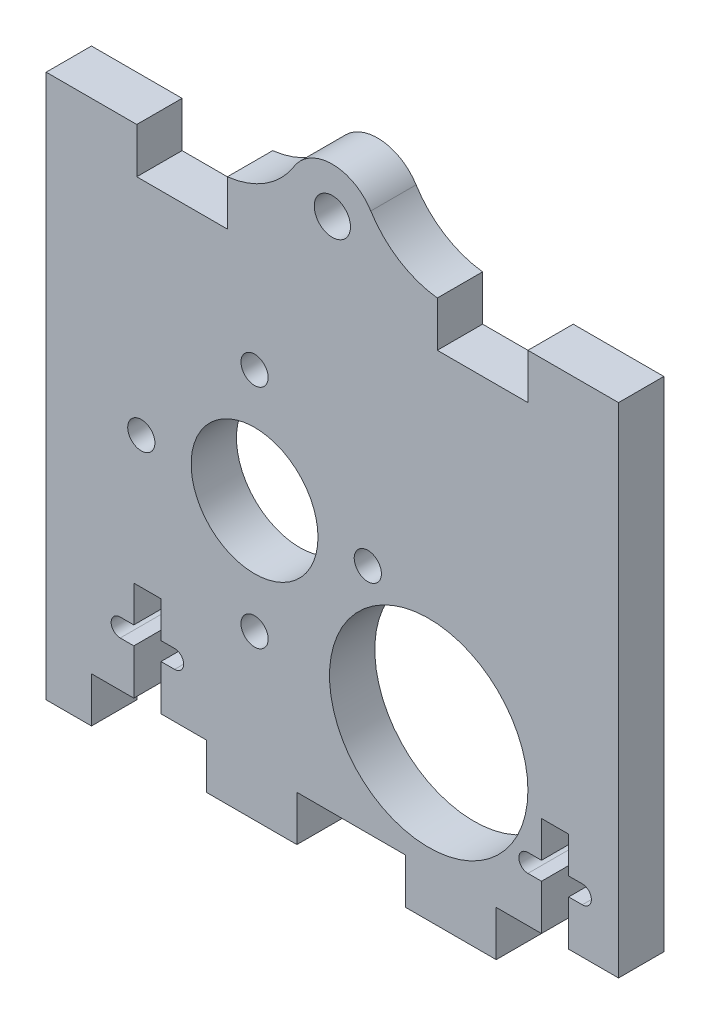
SolidWorks part; units mm, degrees
ref_plane "Front Plane" through (0, 0, 0) normal (0, 0, 1) x (1, 0, 0)
ref_plane "Top Plane" through (0, 0, 0) normal (0, 1, 0) x (1, 0, 0)
ref_plane "Right Plane" through (0, 0, 0) normal (1, 0, 0) x (0, 0, -1)
sketch "Sketch8" plane through (0, 0, 0) normal (0, 0, 1) x (1, 0, 0)
  line L0 (-31.586, -24.275) -> (31.586, -24.275)
  line L1 (-31.586, -24.275) -> (-31.586, 30.725)
  line L2 (-31.586, 30.725) -> (-8.414, 30.725)
  line L3 (31.586, -24.275) -> (31.586, -9.275)
  line L4 (27.586, -18.275) -> (21.586, -18.275) construction
  line L5 (31.586, -24.275) -> (21.586, -24.275)
  line L6 (26.086, -24.275) -> (23.086, -24.275)
  line L7 (26.086, -24.275) -> (26.086, -13.275)
  line L8 (26.086, -13.275) -> (23.086, -13.275)
  line L9 (23.086, -24.275) -> (23.086, -13.275)
  line L10 (27.586, -19.275) -> (21.586, -19.275)
  line L11 (27.586, -17.275) -> (21.586, -17.275)
  line L12 (24.586, -13.275) -> (24.586, -18.275) construction
  line L13 (24.586, -18.275) -> (24.586, -24.275) construction
  line L14 (-18.914, -24.275) -> (-21.914, -24.275)
  line L15 (-18.914, -24.275) -> (-18.914, -13.275)
  line L16 (-18.914, -13.275) -> (-21.914, -13.275)
  line L17 (-21.914, -24.275) -> (-21.914, -13.275)
  line L18 (-20.414, -13.275) -> (-20.414, -18.275) construction
  line L19 (-20.414, -18.275) -> (-20.414, -24.275) construction
  line L20 (-17.414, -18.275) -> (-23.414, -18.275) construction
  line L21 (-17.414, -19.275) -> (-23.414, -19.275)
  line L22 (-17.414, -17.275) -> (-23.414, -17.275)
  line L23 (-17.414, 24.725) -> (-23.414, 24.725) construction
  line L24 (-17.414, 25.725) -> (-23.414, 25.725)
  line L25 (-17.414, 23.725) -> (-23.414, 23.725)
  line L26 (-20.414, 24.725) -> (-20.414, 30.725) construction
  line L27 (-20.414, 19.725) -> (-20.414, 24.725) construction
  line L28 (-21.914, 30.725) -> (-21.914, 19.725)
  line L29 (-18.914, 19.725) -> (-21.914, 19.725)
  line L30 (-18.914, 30.725) -> (-18.914, 19.725)
  line L31 (-18.914, 30.725) -> (-21.914, 30.725)
  circle A0 centre (-8.586, 1.275) radius 7
  circle A1 centre (10.636, -11.325) radius 10.95
  circle A2 centre (-8.586, 13.775) radius 1.5
  circle A3 centre (3.914, 1.275) radius 1.5
  circle A4 centre (-8.586, -11.225) radius 1.5
  circle A5 centre (-21.086, 1.275) radius 1.5
  arc A6 (-8.414, 30.725) -> (31.586, -9.275) centre (-8.414, -9.275) cw
  arc A7 (27.586, -19.275) -> (27.586, -17.275) centre (27.586, -18.275) ccw
  arc A8 (21.586, -17.275) -> (21.586, -19.275) centre (21.586, -18.275) ccw
  arc A9 (-17.414, -19.275) -> (-17.414, -17.275) centre (-17.414, -18.275) ccw
  arc A10 (-23.414, -17.275) -> (-23.414, -19.275) centre (-23.414, -18.275) ccw
  arc A11 (-17.414, 25.725) -> (-17.414, 23.725) centre (-17.414, 24.725) cw
  arc A12 (-23.414, 23.725) -> (-23.414, 25.725) centre (-23.414, 24.725) cw
  point P25 (24.586, -18.275)
  point P41 (-20.414, -18.275)
  point P51 (-20.414, 24.725)
  dimension "D1" = 14
  dimension "D2" = 40
  dimension "D3" = 3
  dimension "D4" = 11
  dimension "D5" = 2
  dimension "D6" = 8
  dimension "D7" = 5
  dimension "D8" = 55
extrude "Boss-Extrude1" add sketch "Sketch8" along normal blind 5 contours L25 A12 L24 L28 L2 L1 L0 L17 L21 A10 L22 L16 L15 A9 L9 L10 A8 L11 L8 L7 A7 L3 A6 L30 A11 L29 A5 A4 A3 A2 region at (-30.7484, 3.225, 0)
sketch "Sketch9" plane through (0, 0, 0) normal (0, 0, -1) x (-1, 0, 0)
  line L0 (18.914, -24.275) -> (-23.086, -24.275) construction
  line L1 (-18.086, -24.275) -> (-8.086, -24.275)
  line L2 (-18.086, -24.275) -> (-18.086, -29.275)
  line L3 (-18.086, -29.275) -> (-8.086, -29.275)
  line L4 (-8.086, -24.275) -> (-8.086, -29.275)
  line L5 (-23.086, -24.275) -> (-23.086, -19.275) construction
  line L6 (3.914, -24.275) -> (3.914, -29.275)
  line L7 (3.914, -24.275) -> (13.914, -24.275)
  line L8 (13.914, -24.275) -> (13.914, -29.275)
  line L9 (3.914, -29.275) -> (13.914, -29.275)
  line L10 (18.914, -24.275) -> (18.914, -19.275) construction
  line L11 (-31.586, -24.275) -> (-31.586, -9.275) construction
  line L12 (31.586, 30.725) -> (-31.586, 30.725)
  line L13 (31.586, 30.725) -> (31.586, 11.7466)
  line L14 (31.586, 11.7466) -> (10.7623, 11.7466)
  line L15 (-31.586, 30.725) -> (-31.586, 11.7466)
  line L16 (6.4097, 11.7466) -> (-17.7432, 11.7466)
  line L19 (-31.586, 11.7466) -> (-31.586, -2.995)
  line L20 (31.586, -24.275) -> (26.586, -24.275)
  line L21 (31.586, -24.275) -> (31.586, -29.275)
  line L22 (31.586, -29.275) -> (26.586, -29.275)
  line L23 (26.586, -24.275) -> (26.586, -29.275)
  line L24 (-26.161, -2.995) -> (-17.7432, -2.995)
  line L25 (-17.7432, 11.7466) -> (-17.7432, -2.995)
  line L26 (-31.586, -9.275) -> (-26.161, -9.275)
  line L27 (-31.586, -9.275) -> (-31.586, -2.995)
  line L29 (-26.161, -9.275) -> (-26.161, -2.995)
  arc A0 (10.7623, 11.7466) -> (6.4097, 11.7466) centre (8.586, 13.775) ccw
  circle A1 centre (-10.636, -11.325) radius 10.95 construction
  dimension "D1" = 5
  dimension "D2" = 5
  dimension "D3" = 10
  dimension "D5" = 5
  dimension "D10" = 5
  dimension "D4" = 2
extrude "Boss-Extrude2" add sketch "Sketch9" against normal blind 5
sketch "Sketch10" plane through (0, 0, 0) normal (0, 0, -1) x (-1, 0, 0)
  arc A0 (0.2424, -12.5751) -> (-7.4428, -0.8509) centre (8.586, 1.275) ccw
  arc A1 (0.2424, -12.5751) -> (-7.4428, -0.8509) centre (-10.636, -11.325) ccw
extrude "Boss-Extrude3" [suppressed] add sketch "Sketch10" against normal blind 5
sketch "Sketch11" plane through (0, 0, 5) normal (0, 0, 1) x (1, 0, 0)
  line L0 (-31.586, 30.725) -> (31.586, 30.725) construction
  line L1 (-21.586, 30.725) -> (-11.586, 30.725)
  line L2 (-21.586, 30.725) -> (-21.586, 25.725)
  line L3 (-21.586, 25.725) -> (-11.586, 25.725)
  line L4 (-11.586, 30.725) -> (-11.586, 25.725)
  line L5 (-31.586, -29.275) -> (-31.586, 30.725) construction
  line L6 (21.586, 30.725) -> (11.586, 30.725)
  line L7 (21.586, 30.725) -> (21.586, 25.725)
  line L8 (21.586, 25.725) -> (11.586, 25.725)
  line L9 (11.586, 30.725) -> (11.586, 25.725)
  line L10 (31.586, -24.275) -> (31.586, 30.725) construction
  line L11 (-11.586, 32.725) -> (11.586, 32.725) construction
  circle A0 centre (0, 32.725) radius 2
  circle A1 centre (0, 32.725) radius 5
  line M2 (31.586, 30.725) -> (-31.586, 30.725)
  dimension "D5" = 4
  dimension "D1" = 5
  dimension "D2" = 10
  dimension "D3" = 10
  dimension "D4" = 10
extrude "Boss-Extrude4" add sketch "Sketch11" against normal blind 5
extrude "Cut-Extrude1" cut sketch "Sketch11<2>" against normal blind 5 contours L4 L2 L3 M2 | L9 L8 L7 M2 region at (16.586, 28.225, 5) region at (-16.586, 28.225, 5)
sketch "Sketch11<2>" plane through (0, 0, 5) normal (0, 0, 1) x (1, 0, 0) same geometry as "Sketch11"
fillet "Fillet1" [suppressed] radius 10
fillet "Fillet2" radius 10 2 edges at (4.5826, 30.725, 2.5) (-4.5826, 30.725, 2.5)
